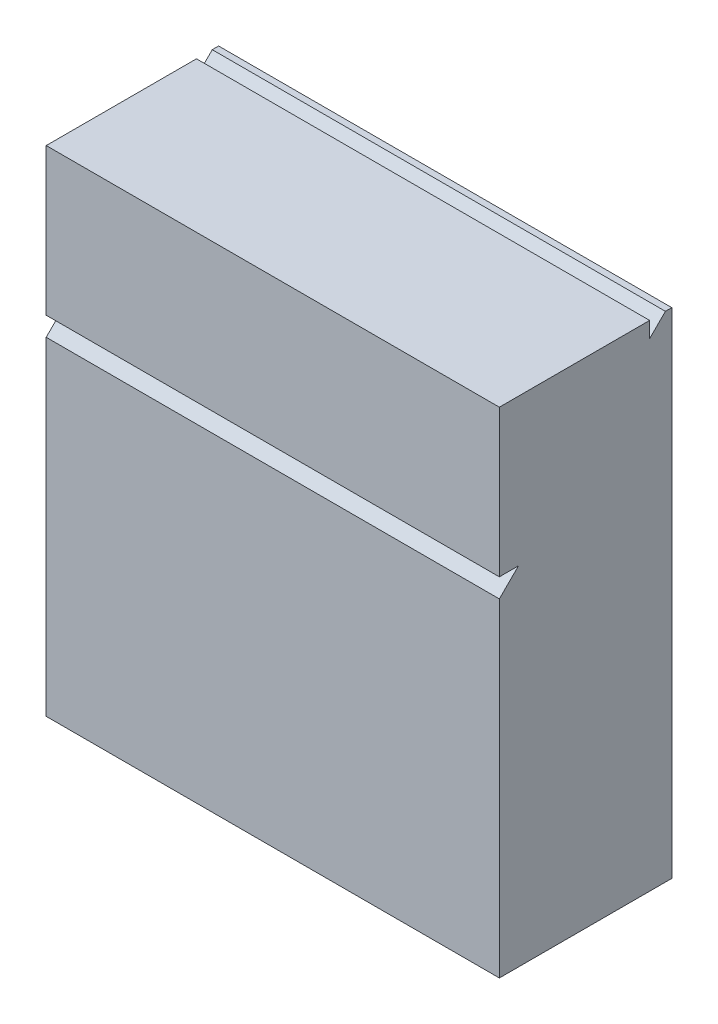
SolidWorks part; units mm, degrees
material "Glass"
ref_plane "Front Plane" through (0, 0, 0) normal (0, 0, 1) x (1, 0, 0)
ref_plane "Top Plane" through (0, 0, 0) normal (0, 1, 0) x (1, 0, 0)
ref_plane "Right Plane" through (0, 0, 0) normal (1, 0, 0) x (0, 0, -1)
sketch "Sketch1" plane through (0, 0, 0) normal (0, 0, 1) x (1, 0, 0)
  line L1 (-11, -12) -> (11, -12)
  line L2 (-11, -12) -> (-11, 12)
  line L3 (-11, 12) -> (11, 12)
  line L4 (11, -12) -> (11, 12)
  line L5 (-11, -12) -> (11, 12) construction
  line L6 (-11, 12) -> (11, -12) construction
  point P0 (0, 0)
  dimension "D1" = 22
  dimension "D2" = 24
extrude "Boss-Extrude1" add sketch "Sketch1" along normal blind 8.371
sketch "Sketch5" plane through (11, 0, 0) normal (1, 0, 0) x (0, 0, -1)
  line L0 (-0.31, 12) -> (-8.371, 3.939)
  line L1 (-8.371, 12) -> (0, 12) construction
  line L2 (-8.371, -12) -> (-8.371, 12) construction
  dimension "D1" = 45
  dimension "D2" = 5.7
extrude "Cut-Extrude2" cut sketch "Sketch5" against normal through all and the other way through all flip side to cut
sketch "Sketch6" plane through (11, 0, 0) normal (1, 0, 0) x (0, 0, -1)
  line L0 (-0.31, 12) -> (-11.409, 12) construction
  line L1 (-8.371, 3.939) -> (-8.371, 12.3044) construction
  line L2 (-0.31, 12) -> (-8.371, 3.939) construction
  line L3 (-8.371, 12) -> (-1.0754, 12)
  line L4 (-8.371, 12) -> (-8.371, 4.8658)
  line L5 (-8.371, 4.8658) -> (-7.4441, 4.8658)
  line L6 (-1.0754, 12) -> (-1.0754, 11.2346)
  line L7 (-1.0754, 11.2346) -> (-7.4441, 4.8658)
extrude "Boss-Extrude3" add sketch "Sketch6" against normal through all
ref_plane "Plane1" through (0, 9, 0) normal (0, 1, 0) x (1, 0, 0)
ref_plane "Plane2" through (-1, 0, 0) normal (1, 0, 0) x (0, 0, -1)
ref_axis "Axis1" through (-1, 9, 33.6629) along (0, 0, -1)
ref_point "Point1"
ref_plane "Plane3" through (0, 6.155, 6.155) normal (0, 0.7071, 0.7071) x (1, 0, 0)
